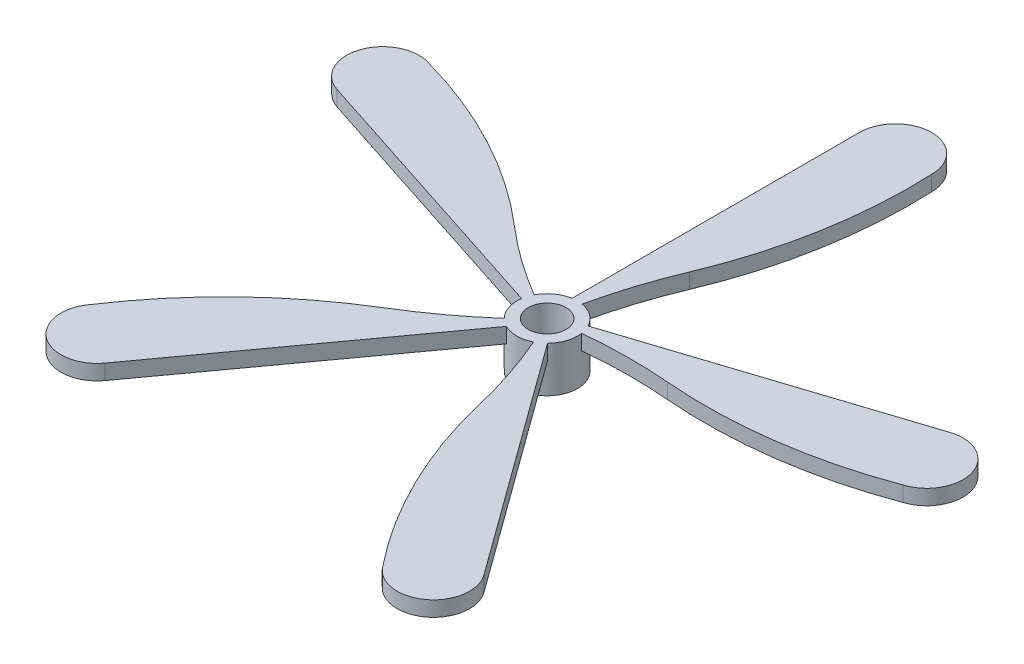
SolidWorks part; units mm, degrees
ref_plane "Front Plane" through (0, 0, 0) normal (0, 0, 1) x (1, 0, 0)
ref_plane "Top Plane" through (0, 0, 0) normal (0, 1, 0) x (1, 0, 0)
ref_plane "Right Plane" through (0, 0, 0) normal (1, 0, 0) x (0, 0, -1)
sketch "Sketch1" plane through (0, 0, 0) normal (0, 1, 0) x (1, 0, 0)
  circle A0 centre (0, 0) radius 2.5
  circle A1 centre (0, 0) radius 4
extrude "Boss-Extrude1" add sketch "Sketch1" along normal blind 6
sketch "Sketch2" plane through (0, 6, 0) normal (0, 1, 0) x (1, 0, 0)
  line L0 (-0.6594, 3.9453) -> (-0.6594, 41.8039)
  circle A0 centre (0, 0) radius 4 construction
  arc A1 (-0.6594, 41.8039) -> (8.8821, 41.7523) centre (4.1115, 41.8039) cw
  arc A2 (8.8821, 41.7523) -> (4.0581, 14.6724) centre (-54.041, 38.9918) cw
  arc A3 (4.0581, 14.6724) -> (0.6594, 3.9453) centre (62.0594, -9.6061) ccw
  arc A4 (0.6594, 3.9453) -> (-0.6594, 3.9453) centre (0, 0) ccw
extrude "Boss-Extrude2" add sketch "Sketch2" against normal blind 2
ref_axis "Axis1" through (0, -0.3, 0) along (0, 1, 0)
pattern_circular "CirPattern1" count 5 over 360 about axis through (0, -0.3, 0) along (0, 1, 0) of "Boss-Extrude2"
